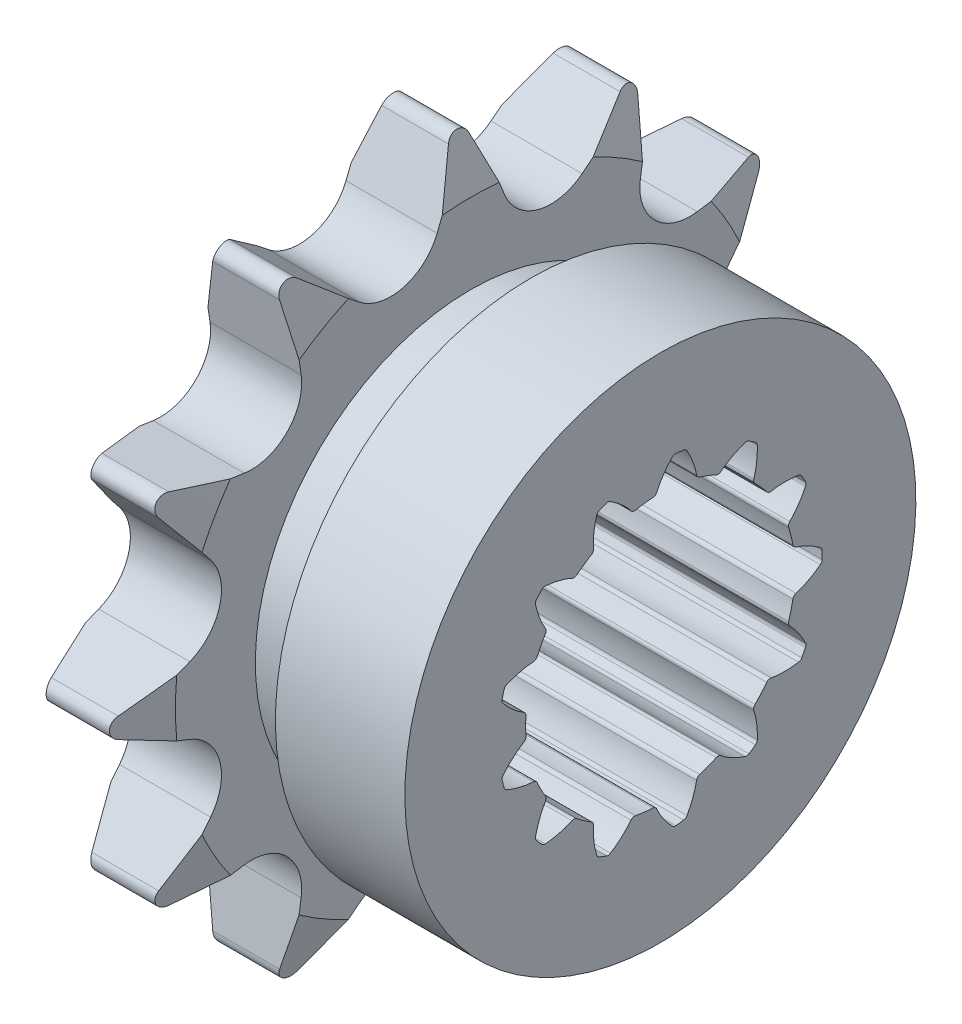
SolidWorks part; units mm, degrees
material "1144"
ref_plane "Front Plane" through (0, 0, 0) normal (0, 0, 1) x (1, 0, 0)
ref_plane "Top Plane" through (0, 0, 0) normal (0, 1, 0) x (1, 0, 0)
ref_plane "Right Plane" through (0, 0, 0) normal (1, 0, 0) x (0, 0, -1)
ref_axis "Axis1" through (-63.0158, 0, 0) along (1, 0, 0)
sketch "Sketch1" plane through (0, 0, 0) normal (0, 0, 1) x (1, 0, 0)
  line L0 (3.6068, 17.0561) -> (3.6068, 0) construction
  line L1 (22.225, 0) -> (22.225, 20.2311)
  line L3 (7.2136, 17.0561) -> (0, 17.0561)
  line L7 (0, 27.5082) -> (0, 30.0482) construction
  line L8 (0, 27.5082) -> (7.2136, 27.5082)
  line L9 (22.225, 0) -> (0, 0)
  line L10 (0, 0) -> (-84.1773, 0) construction
  line L11 (0, 17.0561) -> (0, 27.5082) construction
  line L12 (7.2136, 27.5082) -> (73.2462, 27.5082) construction
  line L13 (22.225, 0) -> (22.225, -20.2311) construction
  line L14 (3.6068, 0) -> (3.6068, -17.0561)
  line L15 (-15.4432, -17.0561) -> (22.6568, -17.0561)
  point P11 (0, 30.0482)
  dimension "D1" = 2.54
  dimension "hub_dia" = 40.4622
  dimension "width_teetth" = 7.2136
  dimension "D2" = 38.1
  dimension "length_thru" = 22.225
  dimension "OD" = 55.0164
  dimension "length_over_teeth" = 7.2136
  dimension "recess_hub_diam" = 34.1122
  dimension "hub_type" = 22.225
  dimension "projection 1" = 15.0114
  dimension "projection 2" = 0
sketch "Sketch2" plane through (0, 0, 0) normal (1, 0, 0) x (0, 0, -1)
  line L0 (0, 0) -> (0, 27.5082) construction
  line L1 (0, 0) -> (-13.7541, 23.8228) construction
  line L2 (0, 0) -> (-6.3502, 23.6991) construction
  line L3 (-0.8057, 26.9597) -> (-2.6638, 22.246)
  line L4 (-2.6638, 22.246) -> (-6.3502, 23.6991) construction
  line L5 (-0.8217, 27.4959) -> (0, 0) construction
  line L6 (-2.735, 27.3719) -> (0, 0) construction
  line L7 (-6.3502, 23.6991) -> (-2.4074, 24.0931) construction
  arc A1 (0, 27.5082) -> (-13.7541, 23.8228) centre (0, 0) ccw
  circle A2 centre (0, 0) radius 24.5351 construction
  circle A3 centre (-6.3502, 23.6991) radius 3.9624
  arc A4 (0, 27.5082) -> (-0.8057, 26.9597) centre (0, 26.6421) ccw
  dimension "pitch_diam" = 49.0703
  dimension "roller_diam" = 7.9248
  dimension "D1" = 1.712
  dimension "ang_1" = 30
  dimension "OD/2" = 27.5082
sketch "Taper Per Foot" plane through (0, 0, 0) normal (0, 0, 1) x (1, 0, 0)
  line L0 (22.225, 0) -> (22.225, 127)
  line L1 (22.225, 0) -> (22.225, 20.2311) construction
  line L2 (22.225, 127) -> (-282.575, 6.35)
  line L3 (-282.575, 6.35) -> (-282.575, 0)
  line L4 (-282.575, 0) -> (22.225, 0)
  line L5 (-282.575, 0) -> (-285.7823, 0) construction
  line L6 (-282.575, 6.35) -> (22.225, 6.35)
  line L7 (22.225, 6.35) -> (22.225, 127)
  dimension "1 Ft" = 304.8
  dimension "1 in" = 254
  dimension "Small End Diam" = 12.7
  dimension "Large End Diam" = 12.7
ref_plane "Plane1" through (7.2136, 0, 0) normal (1, 0, 0) x (0, 0, -1)
ref_plane "Plane2" through (7.2136, 0, 0) normal (1, 0, 0) x (0, 0, -1)
ref_plane "Plane3" through (0, 17.0561, 0) normal (-1, 0, 0) x (0, 0, 1)
ref_plane "Plane4" through (22.225, 0, 0) normal (1, 0, 0) x (0, 0, -1)
ref_plane "Plane5" through (3.6068, 0, 0) normal (1, 0, 0) x (0, 0, -1)
sketch "Sketch13" plane through (0, 0, 0) normal (0, 0, 1) x (1, 0, 0)
  line L0 (22.225, 0) -> (22.225, 20.2311) construction
  line L1 (0, 0) -> (22.225, 0)
  line L2 (0, 0) -> (0, 27.5082)
  line L3 (0, 27.5082) -> (22.225, 27.5082)
  line L4 (22.225, 0) -> (22.225, 27.5082)
revolve "Revolve1" add sketch "Sketch13" angle 360 about L10
sketch "Sketch6" plane through (0, -16.51, 0) normal (1, 0, 0) x (0, 0, -1)
  line L0 (-0.8057, 43.4697) -> (-2.6638, 38.756) construction
  line L1 (-0.8057, 43.4697) -> (-2.6638, 38.756)
  line L2 (-6.3502, 40.2091) -> (0, 16.51) construction
  line L3 (-12.7821, 40.2607) -> (-8.8161, 37.1075)
  arc A0 (0, 44.0182) -> (-0.8057, 43.4697) centre (0, 43.1521) ccw construction
  arc A1 (0, 44.0182) -> (-0.8057, 43.4697) centre (0, 43.1521) ccw
  arc A2 (-13.7541, 40.3328) -> (-12.7821, 40.2607) centre (-13.3211, 39.5828) cw
  arc A3 (-2.6638, 38.756) -> (-8.8161, 37.1075) centre (-6.3502, 40.2091) cw
  arc A4 (0, 44.0182) -> (-13.7541, 40.3328) centre (0, 16.51) ccw
extrude "Cut-Extrude1" cut sketch "Sketch6" along normal up to vertex (7.2136 mm away) up to point (7.2136, 17.0561, 0)
pattern_circular "CirPattern1" count 12 over 360 about axis through (-63.0158, 0, 0) along (1, 0, 0) of "Cut-Extrude1"
sketch "Sketch15" plane through (0, 0, 0) normal (0, 0, 1) x (1, 0, 0)
  line L1 (134.2136, 20.2311) -> (7.2136, 20.2311)
  line L2 (134.2136, 20.2311) -> (134.2136, 42.7482)
  line L3 (134.2136, 42.7482) -> (7.2136, 42.7482)
  line L4 (7.2136, 20.2311) -> (7.2136, 42.7482)
  line L5 (3.6068, 216.4797) -> (3.6068, 17.0561) construction
  line L6 (-127, 20.2311) -> (0, 20.2311)
  line L7 (0, 20.2311) -> (0, 42.7482)
  line L8 (-127, 42.7482) -> (0, 42.7482)
  line L9 (-127, 20.2311) -> (-127, 42.7482)
  dimension "D1" = 12.7
  dimension "D2" = 127
revolve "hub Cut-Revolve3" cut sketch "Sketch15" angle 360 about L10
sketch "Sketch4" plane through (0, 0, 0) normal (0, 0, 1) x (1, 0, 0)
  line L0 (0, 27.5082) -> (1.1045, 27.5082)
  line L2 (1.1045, 27.5082) -> (0, 23.3861)
  line L4 (0, 23.3861) -> (0, 27.5082)
  line L5 (3.6068, 27.5082) -> (3.6068, 44.9612) construction
  line L6 (7.2136, 27.5082) -> (6.1091, 27.5082)
  line L7 (7.2136, 23.3861) -> (7.2136, 27.5082)
  line L8 (6.1091, 27.5082) -> (7.2136, 23.3861)
  line L9 (0, 0) -> (-52.1231, 0) construction
  line L10 (0, 0) -> (-84.1773, 0) construction
  line L17 (0, 27.5082) -> (7.2136, 27.5082) construction
  dimension "D1" = 15
  dimension "D2" = 4.1221
revolve "Teeth Chamfer" cut sketch "Sketch4" angle 360 about L9
sketch "Sketch16" plane through (0, 0, 0) normal (0, 0, 1) x (1, 0, 0)
  line L1 (7.2136, 20.2311) -> (11.9761, 20.2311)
  line L2 (7.2136, 20.2311) -> (7.2136, 17.0561)
  line L3 (7.2136, 17.0561) -> (11.9761, 17.0561)
  line L4 (11.9761, 20.2311) -> (11.9761, 17.0561)
  line L5 (11.9761, 20.2311) -> (22.225, 20.2311) construction
  dimension "recess_width" = 4.7625
  dimension "recess_height" = 3.175
revolve "Recess" cut sketch "Sketch16" angle 360 about L10
sketch "Sketch31" plane through (0, 0, 0) normal (-1, 0, 0) x (0, 0, 1)
  arc A0 (9.097, -5.6181) -> (9.7313, -4.4292) centre (0, 0) ccw
  arc A1 (9.097, -5.6181) -> (9.0986, -5.9863) centre (9.3955, -5.8008) ccw
  arc A2 (10.055, -4.164) -> (9.7313, -4.4292) centre (10.071, -4.5136) ccw
  arc A3 (12.1705, -3.6562) -> (12.3739, -3.4251) centre (12.0362, -3.333) ccw
  arc A4 (12.3739, -3.4251) -> (12.5248, -2.8127) centre (0.0056, -0.0518) ccw
  arc A5 (9.3895, -8.7865) -> (9.8078, -8.3144) centre (0.0056, -0.0518) ccw
  arc A6 (4.2554, -12.1469) -> (4.8452, -11.9232) centre (0.0056, -0.0518) ccw
  arc A7 (-1.8522, -12.7365) -> (-1.2261, -12.8125) centre (0.0056, -0.0518) ccw
  arc A8 (-7.5343, -10.4201) -> (-7.0152, -10.7784) centre (0.0056, -0.0518) ccw
  arc A9 (-11.489, -5.7285) -> (-11.1959, -6.287) centre (0.0056, -0.0518) ccw
  arc A10 (-12.8144, -0.0518) -> (-12.8105, -0.3671) centre (0.0056, -0.0518) ccw
  arc A11 (12.533, -2.7373) -> (12.4521, -2.5135) centre (12.183, -2.7373) ccw
  arc A12 (12.5248, -2.8127) -> (12.533, -2.7373) centre (12.183, -2.7373) ccw
  arc A13 (10.6424, -0.7555) -> (10.815, -1.0808) centre (10.9916, -0.7786) ccw
  arc A14 (10.6424, -0.7555) -> (10.6656, -0.0518) centre (0.0056, -0.0518) ccw
  arc A15 (10.6656, -0.0518) -> (10.6424, 0.6519) centre (0.0056, -0.0518) ccw
  arc A16 (10.815, 0.9772) -> (10.6424, 0.6519) centre (10.9916, 0.6751) ccw
  arc A17 (12.4521, 2.41) -> (12.533, 2.6337) centre (12.183, 2.6337) ccw
  arc A18 (-12.8105, 0.2636) -> (-12.8144, -0.0518) centre (0.0056, -0.0518) ccw
  arc A19 (-11.1959, 6.1834) -> (-11.489, 5.6249) centre (0.0056, -0.0518) ccw
  arc A20 (-7.0152, 10.6748) -> (-7.5343, 10.3165) centre (0.0056, -0.0518) ccw
  arc A21 (-1.2261, 12.7089) -> (-1.8522, 12.6329) centre (0.0056, -0.0518) ccw
  arc A22 (4.8452, 11.8197) -> (4.2554, 12.0433) centre (0.0056, -0.0518) ccw
  arc A23 (9.8078, 8.2108) -> (9.3895, 8.6829) centre (0.0056, -0.0518) ccw
  arc A24 (12.5248, 2.7091) -> (12.3739, 3.3215) centre (0.0056, -0.0518) ccw
  arc A25 (12.533, 2.6337) -> (12.5248, 2.7091) centre (12.183, 2.6337) ccw
  arc A26 (12.3739, 3.3215) -> (12.1705, 3.5526) centre (12.0362, 3.2294) ccw
  arc A27 (9.751, 4.2682) -> (10.055, 4.0604) centre (10.071, 4.4101) ccw
  arc A28 (9.751, 4.2682) -> (9.097, 5.5145) centre (0.0056, -0.0518) ccw
  arc A29 (9.0986, 5.8827) -> (9.097, 5.5145) centre (9.3955, 5.6972) ccw
  arc A30 (9.8901, 7.9852) -> (9.8078, 8.2108) centre (9.5401, 7.9852) ccw
  arc A31 (9.8824, 7.9122) -> (9.8901, 7.9852) centre (9.5401, 7.9852) ccw
  arc A32 (9.3895, 8.6829) -> (9.102, 8.793) centre (9.1333, 8.4444) ccw
  arc A33 (6.6272, 8.3023) -> (5.4688, 9.1018) centre (0.0056, -0.0518) ccw
  arc A34 (6.6272, 8.3023) -> (6.9929, 8.2596) centre (6.8446, 8.5766) ccw
  arc A35 (5.2992, 9.4287) -> (5.4688, 9.1018) centre (5.6482, 9.4024) ccw
  arc A36 (5.0501, 11.5899) -> (4.8452, 11.8197) centre (4.713, 11.4956) ccw
  arc A37 (4.2554, 12.0433) -> (3.9497, 12.0072) centre (4.1394, 11.7131) ccw
  arc A38 (1.9864, 10.4226) -> (0.5891, 10.5922) centre (0.0056, -0.0518) ccw
  arc A39 (1.9864, 10.4226) -> (2.3301, 10.5547) centre (2.0514, 10.7665) ccw
  arc A40 (0.2871, 10.8028) -> (0.5891, 10.5922) centre (0.6083, 10.9417) ccw
  arc A41 (-0.9379, 12.6007) -> (-1.2261, 12.7089) centre (-1.1925, 12.3605) ccw
  arc A42 (-1.8522, 12.6329) -> (-2.1062, 12.4588) centre (-1.8015, 12.2866) ccw
  arc A43 (-3.1082, 10.1433) -> (-4.4242, 9.6442) centre (0.0056, -0.0518) ccw
  arc A44 (-3.1082, 10.1433) -> (-2.8653, 10.42) centre (-3.2104, 10.478) ccw
  arc A45 (-4.7895, 9.6902) -> (-4.4242, 9.6442) centre (-4.5697, 9.9625) ccw
  arc A46 (-6.7097, 10.7129) -> (-7.0152, 10.6748) centre (-6.8235, 10.382) ccw
  arc A47 (-7.5343, 10.3165) -> (-7.6783, 10.0444) centre (-7.3284, 10.0335) ccw
  arc A48 (-7.4894, 7.5284) -> (-7.3855, 7.7773) centre (-7.7355, 7.7773) ccw
  arc A49 (-7.4894, 7.5284) -> (-8.4227, 6.4749) centre (0.0056, -0.0518) ccw
  arc A50 (-7.3855, 7.7773) -> (-7.4029, 7.8863) centre (-7.7355, 7.7773) ccw
  arc A51 (-8.7676, 6.3459) -> (-8.4227, 6.4749) centre (-8.6995, 6.6892) ccw
  arc A52 (-10.9431, 6.3591) -> (-11.1959, 6.1834) centre (-10.8901, 6.0132) ccw
  arc A53 (-11.489, 5.6249) -> (-11.4901, 5.3171) centre (-11.1752, 5.4699) ccw
  arc A54 (-10.1536, 3.177) -> (-10.4904, 1.8105) centre (0.0056, -0.0518) ccw
  arc A55 (-10.1372, 3.2831) -> (-10.2433, 3.5342) centre (-10.4872, 3.2831) ccw
  arc A56 (-10.1536, 3.177) -> (-10.1372, 3.2831) centre (-10.4872, 3.2831) ccw
  arc A57 (-10.7359, 1.536) -> (-10.4904, 1.8105) centre (-10.8351, 1.8716) ccw
  arc A58 (-12.6683, 0.5366) -> (-12.8105, 0.2636) centre (-12.4606, 0.255) ccw
  arc A59 (-12.8105, -0.3671) -> (-12.6683, -0.6402) centre (-12.4606, -0.3585) ccw
  arc A60 (-10.4904, -1.914) -> (-10.7359, -1.6395) centre (-10.8351, -1.9752) ccw
  arc A61 (-10.4904, -1.914) -> (-10.1536, -3.2806) centre (0.0056, -0.0518) ccw
  arc A62 (-10.1372, -3.3866) -> (-10.1536, -3.2806) centre (-10.4872, -3.3866) ccw
  arc A63 (-10.2433, -3.6377) -> (-10.1372, -3.3866) centre (-10.4872, -3.3866) ccw
  arc A64 (-11.4901, -5.4206) -> (-11.489, -5.7285) centre (-11.1752, -5.5735) ccw
  arc A65 (-11.1959, -6.287) -> (-10.9431, -6.4627) centre (-10.8901, -6.1167) ccw
  arc A66 (-8.4227, -6.5785) -> (-8.7676, -6.4495) centre (-8.6995, -6.7928) ccw
  arc A67 (-8.4227, -6.5785) -> (-7.4894, -7.632) centre (0.0056, -0.0518) ccw
  arc A68 (-7.3855, -7.8809) -> (-7.4894, -7.632) centre (-7.7355, -7.8809) ccw
  arc A69 (-7.4029, -7.9899) -> (-7.3855, -7.8809) centre (-7.7355, -7.8809) ccw
  arc A70 (-7.6783, -10.148) -> (-7.5343, -10.4201) centre (-7.3284, -10.137) ccw
  arc A71 (-7.0152, -10.7784) -> (-6.7097, -10.8165) centre (-6.8235, -10.4855) ccw
  arc A72 (-4.4242, -9.7478) -> (-4.7895, -9.7938) centre (-4.5697, -10.0661) ccw
  arc A73 (-4.4242, -9.7478) -> (-3.1082, -10.2469) centre (0.0056, -0.0518) ccw
  arc A74 (-2.8653, -10.5236) -> (-3.1082, -10.2469) centre (-3.2104, -10.5816) ccw
  arc A75 (-2.1062, -12.5624) -> (-1.8522, -12.7365) centre (-1.8015, -12.3901) ccw
  arc A76 (-1.2261, -12.8125) -> (-0.9379, -12.7043) centre (-1.1925, -12.4641) ccw
  arc A77 (0.5891, -10.6958) -> (1.9864, -10.5262) centre (0.0056, -0.0518) ccw
  arc A78 (0.5891, -10.6958) -> (0.2871, -10.9063) centre (0.6083, -11.0453) ccw
  arc A79 (2.3301, -10.6583) -> (1.9864, -10.5262) centre (2.0514, -10.8701) ccw
  arc A80 (3.9497, -12.1108) -> (4.2554, -12.1469) centre (4.1394, -11.8167) ccw
  arc A81 (4.8452, -11.9232) -> (5.0501, -11.6935) centre (4.713, -11.5991) ccw
  arc A82 (5.4688, -9.2054) -> (5.2992, -9.5322) centre (5.6482, -9.506) ccw
  arc A83 (5.4688, -9.2054) -> (6.6272, -8.4059) centre (0.0056, -0.0518) ccw
  arc A84 (6.9929, -8.3632) -> (6.6272, -8.4059) centre (6.8446, -8.6802) ccw
  arc A85 (9.102, -8.8966) -> (9.3895, -8.7865) centre (9.1333, -8.548) ccw
  arc A86 (9.8078, -8.3144) -> (9.8901, -8.0888) centre (9.5401, -8.0888) ccw
  arc A87 (9.8901, -8.0888) -> (9.8824, -8.0157) centre (9.5401, -8.0888) ccw
  spline S0 degree 4 poles (9.0986, -5.9863) (9.1513, -6.0706) (9.2437, -6.2285) (9.367, -6.4648) (9.5091, -6.7844) (9.6282, -7.0962) (9.741, -7.4422) (9.814, -7.7129) (9.8587, -7.9047) (9.8824, -8.0157) knots 0 0 0 0 0 0.181969 0.334561 0.487154 0.639745 0.792337 1 1 1 1 1 weights 1 1 1 1 1 1 1 1 1 1
  spline S1 degree 4 poles (10.055, -4.164) (10.1544, -4.1595) (10.3368, -4.1458) (10.6013, -4.113) (10.9451, -4.0484) (11.2693, -3.9693) (11.6181, -3.8656) (11.8824, -3.7718) (12.0657, -3.6997) (12.1705, -3.6562) knots 0 0 0 0 0 0.181969 0.334561 0.487154 0.639745 0.792337 1 1 1 1 1 weights 1 1 1 1 1 1 1 1 1 1
  spline S2 degree 4 poles (10.815, -1.0808) (10.9008, -1.131) (11.056, -1.2278) (11.275, -1.3798) (11.5494, -1.5968) (11.7997, -1.8175) (12.0603, -2.0714) (12.2508, -2.2773) (12.3796, -2.4263) (12.4521, -2.5135) knots 0 0 0 0 0 0.181969 0.334561 0.487154 0.639745 0.792337 1 1 1 1 1 weights 1 1 1 1 1 1 1 1 1 1
  spline S3 degree 4 poles (10.815, 0.9772) (10.9008, 1.0274) (11.056, 1.1243) (11.275, 1.2762) (11.5494, 1.4932) (11.7997, 1.714) (12.0603, 1.9678) (12.2508, 2.1737) (12.3796, 2.3227) (12.4521, 2.41) knots 0 0 0 0 0 0.181969 0.334561 0.487154 0.639745 0.792337 1 1 1 1 1 weights 1 1 1 1 1 1 1 1 1 1
  spline S4 degree 4 poles (10.055, 4.0604) (10.1544, 4.0559) (10.3368, 4.0422) (10.6013, 4.0095) (10.9451, 3.9448) (11.2693, 3.8657) (11.6181, 3.762) (11.8824, 3.6683) (12.0657, 3.5962) (12.1705, 3.5526) knots 0 0 0 0 0 0.181969 0.334561 0.487154 0.639745 0.792337 1 1 1 1 1 weights 1 1 1 1 1 1 1 1 1 1
  spline S5 degree 4 poles (9.0986, 5.8827) (9.1513, 5.967) (9.2437, 6.1249) (9.367, 6.3612) (9.5091, 6.6809) (9.6282, 6.9927) (9.741, 7.3386) (9.814, 7.6094) (9.8587, 7.8012) (9.8824, 7.9122) knots 0 0 0 0 0 0.181969 0.334561 0.487154 0.639745 0.792337 1 1 1 1 1 weights 1 1 1 1 1 1 1 1 1 1
  spline S6 degree 4 poles (6.9929, 8.2596) (7.083, 8.3017) (7.2508, 8.3744) (7.5002, 8.4683) (7.8347, 8.5709) (8.1586, 8.6515) (8.5156, 8.7218) (8.7932, 8.7616) (8.989, 8.7829) (9.102, 8.793) knots 0 0 0 0 0 0.181969 0.334561 0.487154 0.639745 0.792337 1 1 1 1 1 weights 1 1 1 1 1 1 1 1 1 1
  spline S7 degree 4 poles (5.2992, 9.4287) (5.3067, 9.5278) (5.3151, 9.7106) (5.3144, 9.9771) (5.2917, 10.3262) (5.2522, 10.6576) (5.1914, 11.0163) (5.1302, 11.29) (5.0807, 11.4806) (5.0501, 11.5899) knots 0 0 0 0 0 0.181969 0.334561 0.487154 0.639745 0.792337 1 1 1 1 1 weights 1 1 1 1 1 1 1 1 1 1
  spline S8 degree 4 poles (2.3301, 10.5547) (2.3902, 10.6339) (2.5051, 10.7763) (2.6823, 10.9753) (2.9308, 11.2215) (3.1801, 11.4434) (3.4636, 11.6716) (3.6909, 11.8358) (3.8543, 11.9457) (3.9497, 12.0072) knots 0 0 0 0 0 0.181969 0.334561 0.487154 0.639745 0.792337 1 1 1 1 1 weights 1 1 1 1 1 1 1 1 1 1
  spline S9 degree 4 poles (0.2871, 10.8028) (0.2476, 10.8941) (0.1701, 11.0598) (0.0457, 11.2954) (-0.1366, 11.594) (-0.3256, 11.8691) (-0.5462, 12.1584) (-0.7276, 12.3723) (-0.86, 12.5181) (-0.9379, 12.6007) knots 0 0 0 0 0 0.181969 0.334561 0.487154 0.639745 0.792337 1 1 1 1 1 weights 1 1 1 1 1 1 1 1 1 1
  spline S10 degree 4 poles (-2.8653, 10.42) (-2.8488, 10.5181) (-2.8133, 10.6975) (-2.7488, 10.9561) (-2.6433, 11.2896) (-2.5256, 11.602) (-2.3806, 11.9357) (-2.2557, 12.1868) (-2.162, 12.36) (-2.1062, 12.4588) knots 0 0 0 0 0 0.181969 0.334561 0.487154 0.639745 0.792337 1 1 1 1 1 weights 1 1 1 1 1 1 1 1 1 1
  spline S11 degree 4 poles (-4.7895, 9.6902) (-4.8669, 9.7527) (-5.0125, 9.8635) (-5.2322, 10.0143) (-5.5324, 10.1939) (-5.8276, 10.3497) (-6.1574, 10.5034) (-6.4174, 10.6085) (-6.6024, 10.676) (-6.7097, 10.7129) knots 0 0 0 0 0 0.181969 0.334561 0.487154 0.639745 0.792337 1 1 1 1 1 weights 1 1 1 1 1 1 1 1 1 1
  spline S12 degree 4 poles (-7.4029, 7.8863) (-7.4339, 7.9809) (-7.4858, 8.1563) (-7.549, 8.4152) (-7.6105, 8.7595) (-7.6514, 9.0908) (-7.6782, 9.4537) (-7.6842, 9.734) (-7.6818, 9.931) (-7.6783, 10.0444) knots 0 0 0 0 0 0.181969 0.334561 0.487154 0.639745 0.792337 1 1 1 1 1 weights 1 1 1 1 1 1 1 1 1 1
  spline S13 degree 4 poles (-8.7676, 6.3459) (-8.8652, 6.3653) (-9.0456, 6.3957) (-9.3102, 6.4271) (-9.6595, 6.4467) (-9.9932, 6.4474) (-10.3567, 6.4302) (-10.6357, 6.4025) (-10.8309, 6.3763) (-10.9431, 6.3591) knots 0 0 0 0 0 0.181969 0.334561 0.487154 0.639745 0.792337 1 1 1 1 1 weights 1 1 1 1 1 1 1 1 1 1
  spline S14 degree 4 poles (-10.2433, 3.5342) (-10.3147, 3.6034) (-10.4422, 3.7346) (-10.6184, 3.9345) (-10.8329, 4.2109) (-11.0231, 4.4851) (-11.2154, 4.794) (-11.3511, 5.0395) (-11.4405, 5.215) (-11.4901, 5.3171) knots 0 0 0 0 0 0.181969 0.334561 0.487154 0.639745 0.792337 1 1 1 1 1 weights 1 1 1 1 1 1 1 1 1 1
  spline S15 degree 4 poles (-10.7359, 1.536) (-10.8312, 1.5078) (-11.0051, 1.4509) (-11.254, 1.3558) (-11.5724, 1.2107) (-11.8683, 1.0563) (-12.1821, 0.8722) (-12.4163, 0.7179) (-12.577, 0.604) (-12.6683, 0.5366) knots 0 0 0 0 0 0.181969 0.334561 0.487154 0.639745 0.792337 1 1 1 1 1 weights 1 1 1 1 1 1 1 1 1 1
  spline S16 degree 4 poles (-10.7359, -1.6395) (-10.8312, -1.6113) (-11.0051, -1.5544) (-11.254, -1.4593) (-11.5724, -1.3143) (-11.8683, -1.1599) (-12.1821, -0.9757) (-12.4163, -0.8214) (-12.577, -0.7076) (-12.6683, -0.6402) knots 0 0 0 0 0 0.181969 0.334561 0.487154 0.639745 0.792337 1 1 1 1 1 weights 1 1 1 1 1 1 1 1 1 1
  spline S17 degree 4 poles (-10.2433, -3.6377) (-10.3147, -3.707) (-10.4422, -3.8382) (-10.6184, -4.0381) (-10.8329, -4.3145) (-11.0231, -4.5887) (-11.2154, -4.8976) (-11.3511, -5.143) (-11.4405, -5.3185) (-11.4901, -5.4206) knots 0 0 0 0 0 0.181969 0.334561 0.487154 0.639745 0.792337 1 1 1 1 1 weights 1 1 1 1 1 1 1 1 1 1
  spline S18 degree 4 poles (-8.7676, -6.4495) (-8.8652, -6.4689) (-9.0456, -6.4993) (-9.3102, -6.5307) (-9.6595, -6.5503) (-9.9932, -6.551) (-10.3567, -6.5338) (-10.6357, -6.506) (-10.8309, -6.4799) (-10.9431, -6.4627) knots 0 0 0 0 0 0.181969 0.334561 0.487154 0.639745 0.792337 1 1 1 1 1 weights 1 1 1 1 1 1 1 1 1 1
  spline S19 degree 4 poles (-7.4029, -7.9899) (-7.4339, -8.0844) (-7.4858, -8.2598) (-7.549, -8.5187) (-7.6105, -8.8631) (-7.6514, -9.1944) (-7.6782, -9.5572) (-7.6842, -9.8376) (-7.6818, -10.0345) (-7.6783, -10.148) knots 0 0 0 0 0 0.181969 0.334561 0.487154 0.639745 0.792337 1 1 1 1 1 weights 1 1 1 1 1 1 1 1 1 1
  spline S20 degree 4 poles (-4.7895, -9.7938) (-4.8669, -9.8563) (-5.0125, -9.9671) (-5.2322, -10.1179) (-5.5324, -10.2975) (-5.8276, -10.4533) (-6.1574, -10.607) (-6.4174, -10.712) (-6.6024, -10.7796) (-6.7097, -10.8165) knots 0 0 0 0 0 0.181969 0.334561 0.487154 0.639745 0.792337 1 1 1 1 1 weights 1 1 1 1 1 1 1 1 1 1
  spline S21 degree 4 poles (-2.8653, -10.5236) (-2.8488, -10.6217) (-2.8133, -10.8011) (-2.7488, -11.0597) (-2.6433, -11.3932) (-2.5256, -11.7056) (-2.3806, -12.0393) (-2.2557, -12.2904) (-2.162, -12.4636) (-2.1062, -12.5624) knots 0 0 0 0 0 0.181969 0.334561 0.487154 0.639745 0.792337 1 1 1 1 1 weights 1 1 1 1 1 1 1 1 1 1
  spline S22 degree 4 poles (0.2871, -10.9063) (0.2476, -10.9976) (0.1701, -11.1634) (0.0457, -11.399) (-0.1366, -11.6976) (-0.3256, -11.9727) (-0.5462, -12.262) (-0.7276, -12.4759) (-0.86, -12.6217) (-0.9379, -12.7043) knots 0 0 0 0 0 0.181969 0.334561 0.487154 0.639745 0.792337 1 1 1 1 1 weights 1 1 1 1 1 1 1 1 1 1
  spline S23 degree 4 poles (2.3301, -10.6583) (2.3902, -10.7375) (2.5051, -10.8799) (2.6823, -11.0789) (2.9308, -11.3251) (3.1801, -11.547) (3.4636, -11.7751) (3.6909, -11.9394) (3.8543, -12.0493) (3.9497, -12.1108) knots 0 0 0 0 0 0.181969 0.334561 0.487154 0.639745 0.792337 1 1 1 1 1 weights 1 1 1 1 1 1 1 1 1 1
  spline S24 degree 4 poles (5.2992, -9.5322) (5.3067, -9.6314) (5.3151, -9.8142) (5.3144, -10.0806) (5.2917, -10.4297) (5.2522, -10.7612) (5.1914, -11.1199) (5.1302, -11.3936) (5.0807, -11.5842) (5.0501, -11.6935) knots 0 0 0 0 0 0.181969 0.334561 0.487154 0.639745 0.792337 1 1 1 1 1 weights 1 1 1 1 1 1 1 1 1 1
  spline S25 degree 4 poles (6.9929, -8.3632) (7.083, -8.4053) (7.2508, -8.478) (7.5002, -8.5719) (7.8347, -8.6744) (8.1586, -8.755) (8.5156, -8.8253) (8.7932, -8.8651) (8.989, -8.8865) (9.102, -8.8966) knots 0 0 0 0 0 0.181969 0.334561 0.487154 0.639745 0.792337 1 1 1 1 1 weights 1 1 1 1 1 1 1 1 1 1
extrude "Spline Cut" cut sketch "Sketch31" against normal through all both and the other way through all
sketch "Sketch32" plane through (22.225, 0, 0) normal (1, 0, 0) x (0, 0, -1)
  circle A1 centre (0, 0) radius 20.2311
  circle A2 centre (0, 0) radius 20.2311
  dimension "D1" = 0
extrude "Collar Reduction" [suppressed] cut sketch "Sketch32" against normal offset from surface (2.455 mm away) 19.77
sketch "Sketch35" [suppressed] plane through (19.77, 0, 0) normal (1, 0, 0) x (0, 0, -1)
  circle A0 centre (-0.0056, -0.0518) radius 15.2995
  circle A1 centre (0, 0) radius 20.2311 construction
  circle A2 centre (0, 0) radius 20.2311
  dimension "D1" = 30.5989
extrude "Cut-Extrude3" [suppressed] cut sketch "Sketch35" against normal blind 1.27
ref_plane "Sprocket Teeth Center" through (3.6068, 0, 0) normal (-1, 0, 0) x (0, 0, 1)
sketch "Sprocket Pitch Circle" plane through (3.6068, 0, 0) normal (-1, 0, 0) x (0, 0, 1)
  circle A0 centre (0.0056, -0.0518) radius 24.535 construction
  dimension "D1" = 49.07
